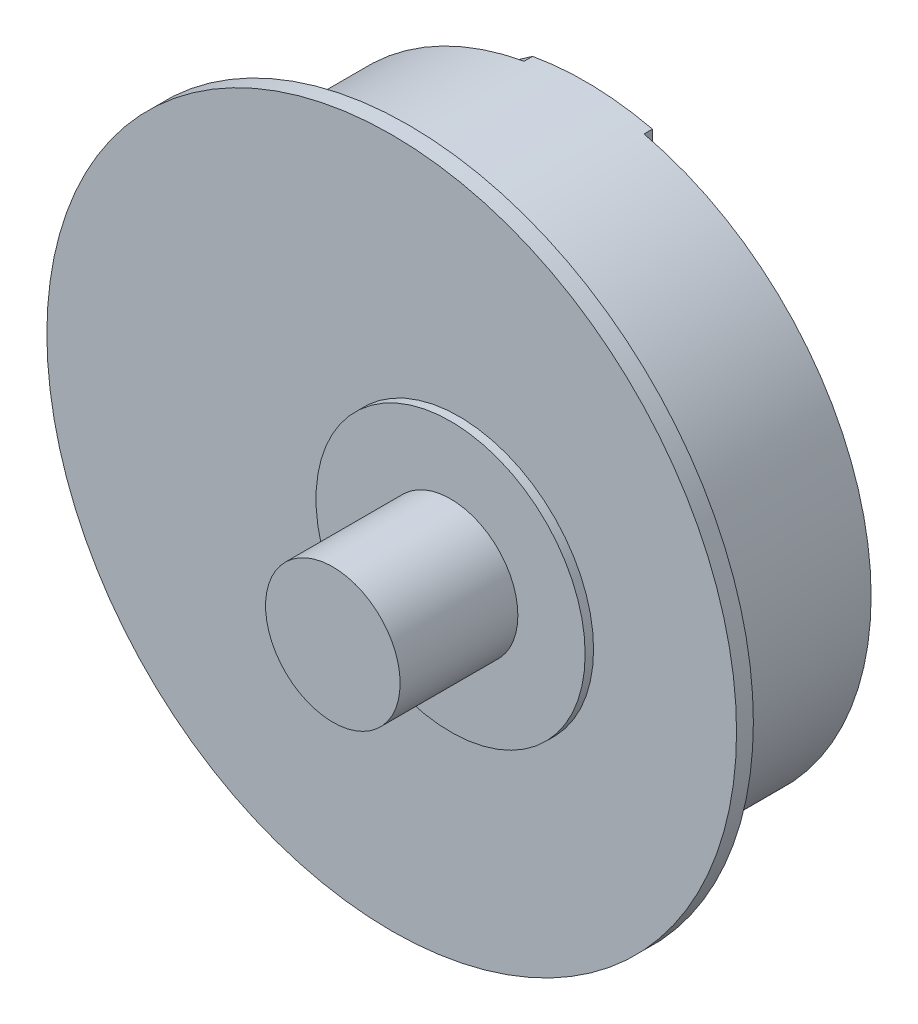
SolidWorks part; units mm, degrees
ref_plane "Front Plane" through (0, 0, 0) normal (0, 0, 1) x (1, 0, 0)
ref_plane "Top Plane" through (0, 0, 0) normal (0, 1, 0) x (1, 0, 0)
ref_plane "Right Plane" through (0, 0, 0) normal (1, 0, 0) x (0, 0, -1)
sketch "Sketch1" plane through (0, 0, 0) normal (0, 0, 1) x (1, 0, 0)
  line L0 (-5, 6.245) -> (-5, -6.245)
  circle A0 centre (0, 0) radius 8
  circle A1 centre (-4, 0) radius 17.5
  dimension "D1" = 35
  dimension "D2" = 16
  dimension "D4" = 5
  dimension "D3" = 4
extrude "Boss-Extrude1" add sketch "Sketch1" along normal blind 5 contours L0 A0 | A1 region at (0.928, 0, 0)
sketch "Sketch6" plane through (0, 0, 5) normal (0, 0, 1) x (1, 0, 0)
  circle A0 centre (-4, 0) radius 17.5
  circle A1 centre (-4, 0) radius 17.5 construction
extrude "Boss-Extrude7" add sketch "Sketch6" along normal blind 5
sketch "Sketch3" plane through (0, 0, 10) normal (0, 0, -1) x (-1, 0, 0)
  circle A0 centre (4, 0) radius 20.5
  circle A2 centre (4, 0) radius 17.5 construction
  dimension "D1" = 41
extrude "Boss-Extrude3" add sketch "Sketch3" against normal blind 1 contours A0 | A0 region at (-4, 0, 10)
sketch "Sketch4" plane through (0, 0, 11) normal (0, 0, 1) x (1, 0, 0)
  circle A0 centre (0, 0) radius 8
  dimension "D1" = 16
extrude "Boss-Extrude5" add sketch "Sketch4" along normal blind 0.5
sketch "Sketch5" plane through (0, 0, 11.5) normal (0, 0, 1) x (1, 0, 0)
  circle A0 centre (0, 0) radius 4
  dimension "D1" = 8
extrude "Boss-Extrude6" add sketch "Sketch5" along normal blind 7
sketch "Sketch7" plane through (0, 0, 0) normal (0, 0, -1) x (-1, 0, 0)
  line L0 (4, 17.5) -> (4, -17.5) construction
  line L1 (4, 0) -> (-4, 0) construction
  line L2 (0, -20.106) -> (0, 20.106)
  circle A2 centre (4, 0) radius 17.5 construction
  circle A3 centre (4, 0) radius 17.5 construction
  circle A4 centre (-4, 0) radius 20.5
  circle A5 centre (4, 0) radius 20.5 construction
  point P7 (0, 0)
  point P15 (0, 0)
  point P16 (0, 0)
  circle M12 centre (4, 0) radius 17.5
  line M13 (5, 6.245) -> (5, -6.245)
  arc M14 (5, -6.245) -> (5, 6.245) centre (0, 0) cw
extrude "Boss-Extrude8" add sketch "Sketch7" along normal blind 0.5 contours A2 | A4 L2 M12 M14 M13 region at (-7.9821, 0, 0)
